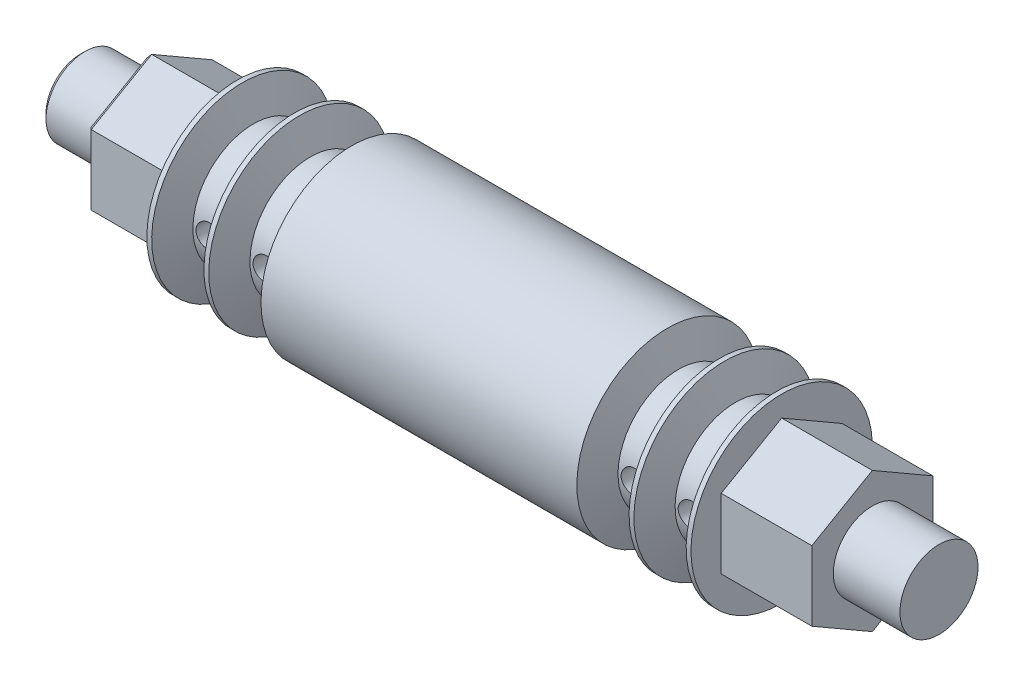
SolidWorks part; units mm, degrees
ref_plane "Front Plane" through (0, 0, 0) normal (0, 0, 1) x (1, 0, 0)
ref_plane "Top Plane" through (0, 0, 0) normal (0, 1, 0) x (1, 0, 0)
ref_plane "Right Plane" through (0, 0, 0) normal (1, 0, 0) x (0, 0, -1)
sketch "Sketch1" plane through (0, 0, 0) normal (0, 0, 1) x (1, 0, 0)
  line L0 (-38.1, 0) -> (38.1, 0) construction
  line L1 (-28.067, 9.525) -> (-26.9114, 6.35)
  line L2 (-26.9114, 6.35) -> (-23.7364, 6.35)
  line L3 (-23.7364, 6.35) -> (-22.5808, 9.525)
  line L4 (-22.5808, 9.525) -> (-22.0728, 9.525)
  line L5 (-22.0728, 9.525) -> (-20.9172, 6.35)
  line L6 (-20.9172, 6.35) -> (-17.7422, 6.35)
  line L7 (-17.7422, 6.35) -> (-16.5866, 9.525)
  line L8 (0, 0) -> (0, 25.6809) construction
  line L9 (-16.5866, 9.525) -> (0, 9.525)
  line L10 (-22.3268, 9.525) -> (-22.3268, 0) construction
  line L11 (-28.575, 9.525) -> (-28.575, 4.354)
  line L12 (-28.575, 4.354) -> (-38.1, 4.354)
  line L13 (-38.1, 4.354) -> (-38.1, 4.1)
  line L14 (-38.1, 0) -> (-28.575, 0)
  line L15 (-28.575, 0) -> (0, 0)
  line L16 (-28.067, 9.525) -> (-28.575, 9.525)
  line L17 (0, 0) -> (0, 9.525)
  line L18 (-38.1, 0) -> (-38.1, -4.1) construction
  line L19 (-28.575, 4.354) -> (-28.575, 0) construction
  line L20 (-45.1, 4.1) -> (-45.1, 0)
  line L21 (-45.1, 4.1) -> (-38.1, 4.1)
  line L22 (-45.1, 0) -> (-45.1, -4.1) construction
  line L23 (-38.1, 4.1) -> (-38.1, 0) construction
  line L24 (-38.1, 0) -> (-45.1, 0)
  dimension "D2" = 3.175
  dimension "D3" = 3.175
  dimension "D4" = 70
  dimension "D6" = 3.175
  dimension "D5" = 0.508
  dimension "D7" = 3.175
  dimension "D8" = 0.508
  dimension "D11" = 9.525
  dimension "D12" = 8.2
  dimension "D13" = 7
  dimension "D10" = 0.254
  dimension "D9" = 76.2
  dimension "D14" = 9.525
revolve "Revolve1" add sketch "Sketch1" angle 360 about L0
sketch "Sketch4" plane through (-28.575, 0, 0) normal (-1, 0, 0) x (0, 0, 1)
  line L1 (0, 7.3323) -> (-6.35, 3.6662)
  line L2 (-6.35, 3.6662) -> (-6.35, -3.6662)
  line L3 (-6.35, -3.6662) -> (0, -7.3323)
  line L4 (0, -7.3323) -> (6.35, -3.6662)
  line L5 (6.35, -3.6662) -> (6.35, 3.6662)
  line L6 (6.35, 3.6662) -> (0, 7.3323)
  circle A0 centre (0, 0) radius 6.35 construction
  dimension "D1" = 12.7
extrude "Boss-Extrude4" add sketch "Sketch4" along normal up to surface (9.525 mm away) up to face at (-38.1, -4.1, 0)
sketch "Sketch6" plane through (0, 0, 0) normal (0, 0, 1) x (1, 0, 0)
  line L0 (-25.3239, 6.35) -> (-25.3239, 0) construction
  line L1 (-26.9114, 6.35) -> (-23.7364, 6.35) construction
  line L2 (-19.3297, 6.35) -> (-19.3297, 0) construction
  line L3 (-20.9172, 6.35) -> (-17.7422, 6.35) construction
  line L4 (-28.575, 0) -> (0, 0) construction
  circle A0 centre (-25.3239, 0) radius 1.27
  circle A1 centre (-19.3297, 0) radius 1.27
  dimension "D1" = 2.54
extrude "Cut-Extrude1" cut sketch "Sketch6" against normal through all both and the other way through all
chamfer "Chamfer2" distance 0.508 angle 45 6 edges at (-38.1, 5.4993, 3.175) (-38.1, 0, 6.35) (-38.1, -5.4993, 3.175) (-38.1, -5.4993, -3.175) (-38.1, 0, -6.35) (-38.1, 5.4993, -3.175)
chamfer "Chamfer3" distance 0.508 angle 45 1 edges at (-45.1, -4.1, 0)
mirror "Mirror1" about plane through (0, 0, 0) normal (1, 0, 0) of "Cut-Extrude1", "Revolve1", "Boss-Extrude4"
equation "\"D12@Sketch1\"=8.2mm"
